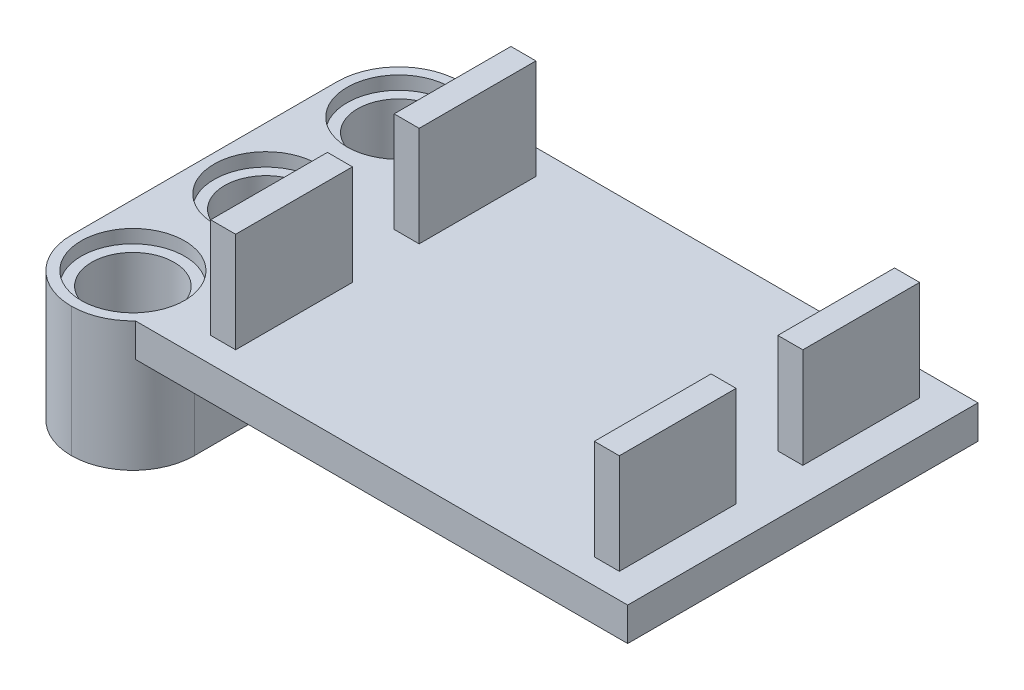
SolidWorks part; units mm, degrees
ref_plane "Front Plane" through (0, 0, 0) normal (0, 0, 1) x (1, 0, 0)
ref_plane "Top Plane" through (0, 0, 0) normal (0, 1, 0) x (1, 0, 0)
ref_plane "Right Plane" through (0, 0, 0) normal (1, 0, 0) x (0, 0, -1)
sketch "Sketch1" plane through (0, 0, 0) normal (0, 1, 0) x (1, 0, 0)
  line L1 (0, 0) -> (28.5, 0)
  line L2 (0, 0) -> (0, 21)
  line L3 (0, 21) -> (28.5, 21)
  line L4 (28.5, 0) -> (28.5, 21)
  dimension "D1" = 21
  dimension "D2" = 28.5
extrude "Boss-Extrude1" add sketch "Sketch1" along normal blind 2
sketch "Sketch2" plane through (0, 2, 0) normal (0, 1, 0) x (1, 0, 0)
  line L0 (0, 0) -> (28.5, 0) construction
  line L1 (2, 19.5) -> (3.5, 19.5)
  line L2 (2, 19.5) -> (2, 12.5)
  line L3 (2, 12.5) -> (3.5, 12.5)
  line L4 (3.5, 19.5) -> (3.5, 12.5)
  line L5 (2, 8.5) -> (3.5, 8.5)
  line L6 (2, 8.5) -> (2, 1.5)
  line L7 (2, 1.5) -> (3.5, 1.5)
  line L8 (3.5, 8.5) -> (3.5, 1.5)
  line L9 (25, 19.5) -> (26.5, 19.5)
  line L10 (25, 19.5) -> (25, 12.5)
  line L11 (25, 12.5) -> (26.5, 12.5)
  line L12 (26.5, 19.5) -> (26.5, 12.5)
  line L13 (25, 8.5) -> (26.5, 8.5)
  line L14 (25, 8.5) -> (25, 1.5)
  line L15 (25, 1.5) -> (26.5, 1.5)
  line L16 (26.5, 8.5) -> (26.5, 1.5)
  line L17 (0, 21) -> (0, 0) construction
  line L18 (28.5, 21) -> (0, 21) construction
  line L19 (28.5, 0) -> (28.5, 21) construction
  dimension "D1" = 1.5
  dimension "D2" = 2
  dimension "D3" = 1.5
  dimension "D4" = 1.5
  dimension "D5" = 1.5
  dimension "D6" = 2
  dimension "D7" = 2
  dimension "D8" = 2
  dimension "D9" = 21.5
  dimension "D10" = 1.5
  dimension "D11" = 21.5
  dimension "D12" = 1.5
  dimension "D13" = 7
  dimension "D14" = 7
  dimension "D15" = 7
  dimension "D16" = 7
extrude "Boss-Extrude2" add sketch "Sketch2" along normal blind 6
sketch "Sketch3" plane through (0, 0, 0) normal (-1, 0, 0) x (0, 0, 1)
  line L0 (-21, 2) -> (0, 2) construction
  line L1 (-22.16, 2) -> (1.16, 2)
  line L2 (-22.16, 2) -> (-22.16, -5.76)
  line L3 (-22.16, -5.76) -> (1.16, -5.76)
  line L4 (1.16, 2) -> (1.16, -5.76)
  line L5 (-21, 2) -> (-21, 0) construction
  dimension "D1" = 23.32
  dimension "D2" = 0
  dimension "D3" = 1.16
  dimension "D4" = 7.76
extrude "Boss-Extrude3" add sketch "Sketch3" along normal blind 7.38
sketch "Sketch4" plane through (0, -5.76, 0) normal (0, -1, 0) x (1, 0, 0)
  line L0 (0, -21) -> (0, 0) construction
  line L1 (-7.38, -22.16) -> (0, -22.16) construction
  line L2 (-7.38, -22.16) -> (-7.38, 1.16) construction
  circle A0 centre (-3.69, -2.53) radius 2.472
  circle A1 centre (-3.69, -10.5) radius 2.472
  circle A2 centre (-3.69, -18.47) radius 2.472
  point P12 (0, 0)
  point P14 (-7.76, -2.9919)
  dimension "D7" = 4.944
  dimension "D8" = 4.944
  dimension "D9" = 4.944
  dimension "D1" = 3.69
  dimension "D2" = 3.69
  dimension "D3" = 7.97
  dimension "D4" = 3.69
  dimension "D5" = 7.97
  dimension "D6" = 3.69
extrude "Cut-Extrude1" cut sketch "Sketch4" against normal blind 7.76
sketch "Sketch5" plane through (0, -5.76, 0) normal (0, -1, 0) x (1, 0, 0)
  circle A0 centre (-3.69, -2.53) radius 3.1
  circle A1 centre (-3.69, -10.5) radius 3.1
  circle A2 centre (-3.69, -18.47) radius 3.1
  dimension "D1" = 6.2
  dimension "D2" = 6.2
  dimension "D3" = 6.2
extrude "Cut-Extrude2" cut sketch "Sketch5" against normal blind 0.8
sketch "Sketch6" plane through (0, 2, 0) normal (0, 1, 0) x (1, 0, 0)
  circle A0 centre (-3.69, 10.5) radius 3.1
  circle A1 centre (-3.69, 18.47) radius 3.1
  circle A2 centre (-3.69, 2.53) radius 3.1
  dimension "D1" = 6.2
  dimension "D2" = 6.2
  dimension "D3" = 6.2
extrude "Cut-Extrude3" cut sketch "Sketch6" against normal blind 0.8
fillet "Fillet1" radius 3.69 4 edges at (-7.38, -1.88, -22.16) (0, -1.88, -22.16) (0, -1.88, 1.16) (-7.38, -1.88, 1.16)
